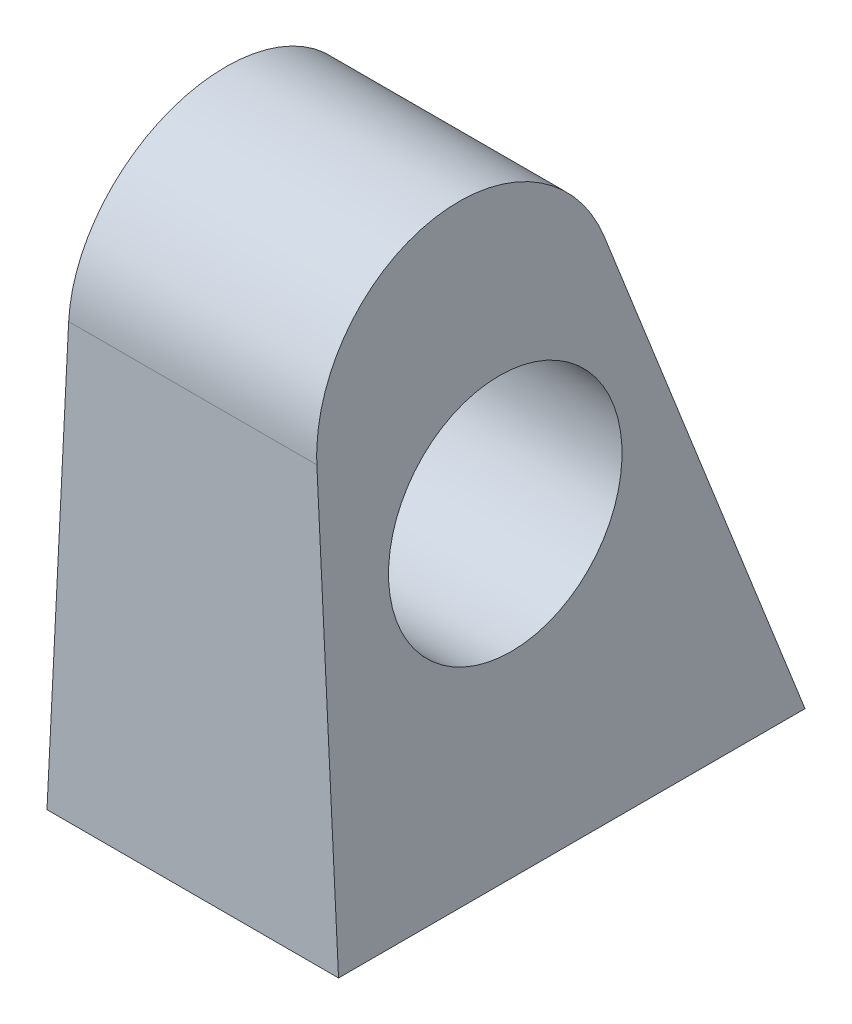
SolidWorks part; units mm, degrees
ref_plane "Front Plane" through (0, 0, 0) normal (0, 0, 1) x (1, 0, 0)
ref_plane "Top Plane" through (0, 0, 0) normal (0, 1, 0) x (1, 0, 0)
ref_plane "Right Plane" through (0, 0, 0) normal (1, 0, 0) x (0, 0, -1)
sketch "Sketch1" plane through (0, 0, 0) normal (1, 0, 0) x (0, 0, -1)
  line L0 (1.547, 13.1962) -> (6.35, 0)
  line L1 (6.35, 0) -> (-6.35, 0)
  line L2 (-6.35, 0) -> (-6.35, 11.8037)
  line L3 (-10.0809, 15.875) -> (13.4038, 15.875) construction
  arc A3 (1.547, 13.1962) -> (-6.35, 11.8037) centre (-2.2787, 11.8037) ccw
  circle A4 centre (-1.3975, 8.2661) radius 3.175
  point P8 (0, 0)
  point P9 (-1.6442, 9.3022)
  point P12 (-1.3975, 8.2661)
  dimension "D1" = 15.875
  dimension "D3" = 70
  dimension "D4" = 6.35
  dimension "D2" = 12.7
extrude "Boss-Extrude1" add sketch "Sketch1" along normal blind 7.9375
sketch "Sketch2" plane through (0, 0, 6.35) normal (0, 0, 1) x (1, 0, 0)
  line L0 (0, 0) -> (7.9375, 0)
  line L1 (7.9375, 0) -> (7.1437, 15.875)
  line L2 (7.9375, 15.875) -> (0, 15.875) construction
  line L3 (7.1437, 15.875) -> (0.7938, 15.875)
  line L4 (0.7938, 15.875) -> (0, 0)
  point P8 (3.9688, 15.875)
  point P9 (3.9688, 0)
  dimension "D1" = 6.35
extrude "Cut-Extrude1" cut sketch "Sketch2" against normal through all flip side to cut
equation "\"D1@Boss-Extrude1\"=5/16in"
